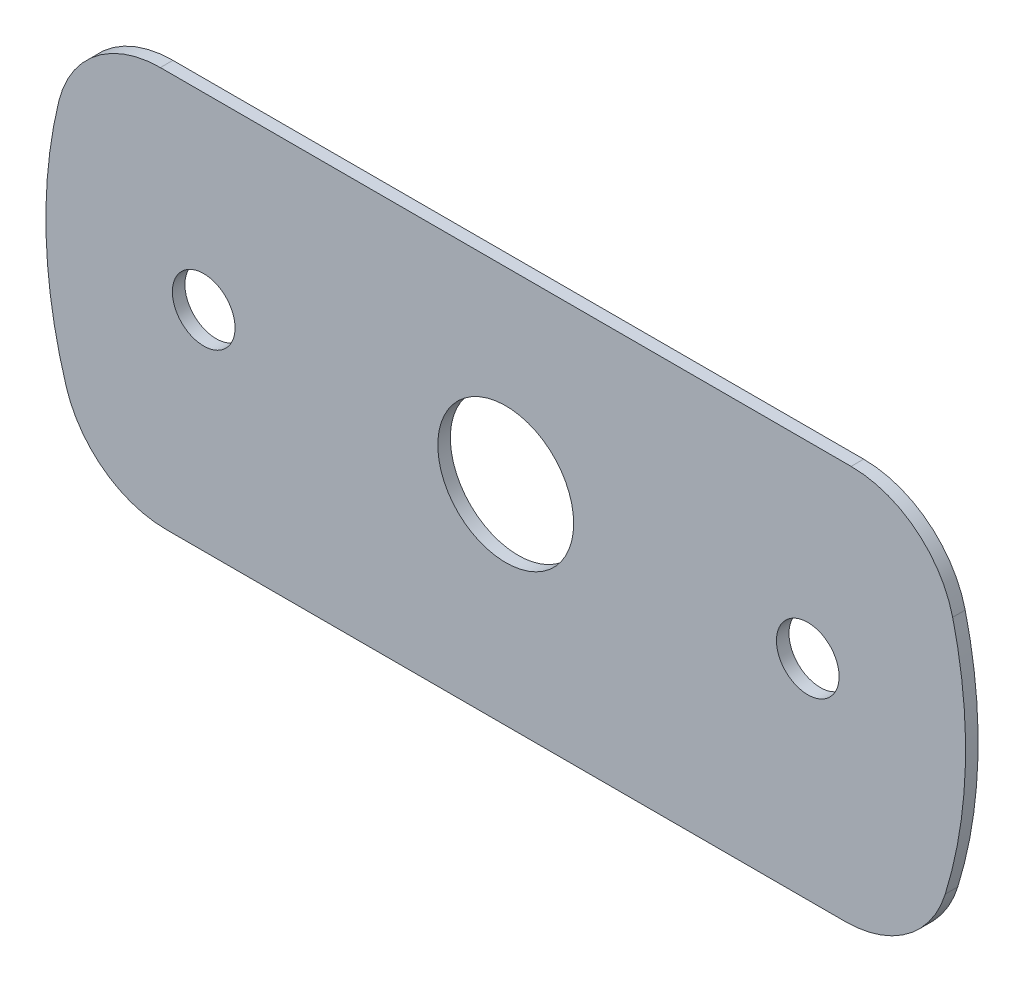
SolidWorks part; units mm, degrees
ref_plane "Спереди" through (0, 0, 0) normal (0, 0, 1) x (1, 0, 0)
ref_plane "Сверху" through (0, 0, 0) normal (0, 1, 0) x (1, 0, 0)
ref_plane "Справа" through (0, 0, 0) normal (1, 0, 0) x (0, 0, -1)
sketch "Эскиз1" plane through (0, 0, 0) normal (0, 0, 1) x (1, 0, 0)
  circle A0 centre (0, 0) radius 22
  dimension "D1" = 44
extrude "Бобышка-Вытянуть1" add sketch "Эскиз1" along normal blind 0.6
sketch "Эскиз2" plane through (0, 0, 0.6) normal (0, 0, 1) x (1, 0, 0)
  circle A0 centre (0, 0) radius 3.25
  dimension "D1" = 6.5
extrude "Вырез-Вытянуть1" cut sketch "Эскиз2" against normal through all
sketch "Эскиз3" plane through (0, 0, 0.6) normal (0, 0, 1) x (1, 0, 0)
  circle A0 centre (-14.45, 0) radius 1.5
  circle A1 centre (14.45, 0) radius 1.5
  dimension "D3" = 3
  dimension "D1" = 0
  dimension "D2" = 14.45
  dimension "D4" = 2
extrude "Вырез-Вытянуть2" cut sketch "Эскиз3" against normal through all
sketch "Эскиз5" plane through (0, 0, 0.6) normal (0, 0, 1) x (1, 0, 0)
  line L1 (-27.9404, 28.515) -> (28.1564, 28.515)
  line L2 (-27.9404, 28.515) -> (-27.9404, 9)
  line L3 (-27.9404, 9) -> (28.1564, 9)
  line L4 (28.1564, 28.515) -> (28.1564, 9)
  line L5 (-27.9404, -10) -> (28.7325, -10)
  line L6 (-27.9404, -10) -> (-27.9404, -31.6754)
  line L7 (-27.9404, -31.6754) -> (28.7325, -31.6754)
  line L8 (28.7325, -10) -> (28.7325, -31.6754)
  dimension "D1" = 19
  dimension "D2" = 10
extrude "Вырез-Вытянуть4" cut sketch "Эскиз5" against normal through all
fillet "Скругление1" radius 5 4 edges at (20.0749, 9, 0.3) (19.5959, -10, 0.3) (-19.5959, -10, 0.3) (-20.0749, 9, 0.3)
